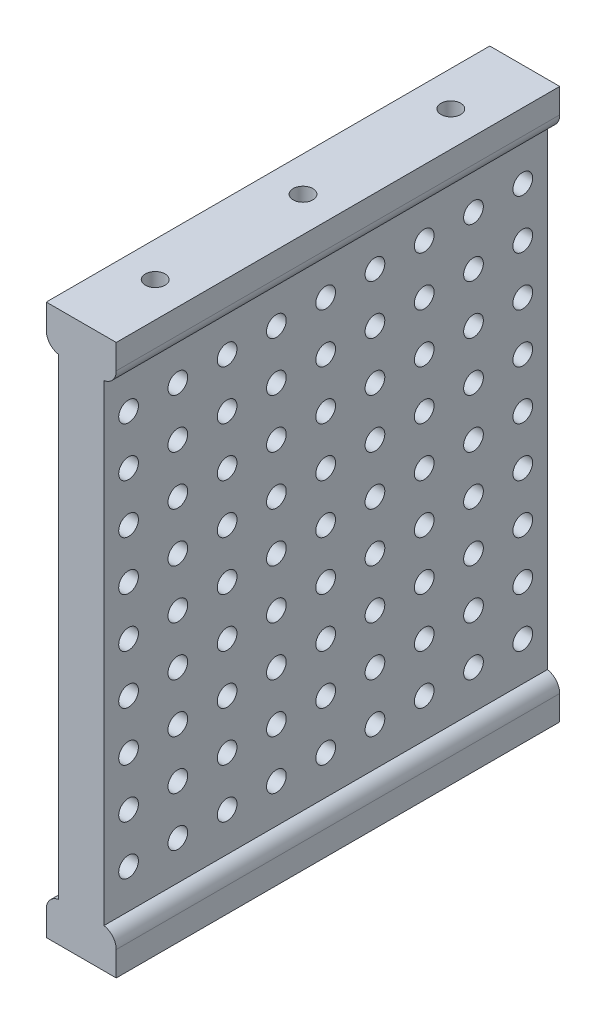
SolidWorks part; units mm, degrees
ref_plane "Plano frontal" through (0, 0, 0) normal (0, 0, 1) x (1, 0, 0)
ref_plane "Plano superior" through (0, 0, 0) normal (0, 1, 0) x (1, 0, 0)
ref_plane "Plano direito" through (0, 0, 0) normal (1, 0, 0) x (0, 0, -1)
sketch "Esboço1" plane through (0, 0, 0) normal (0, 0, 1) x (1, 0, 0)
  line L1 (10.95, -73.1295) -> (10.95, -73.1714)
  line L2 (1.75, -73.1295) -> (1.75, 22.6125)
  line L3 (1.75, 30.5705) -> (10.95, 30.5705)
  line L4 (10.95, -73.1295) -> (10.95, 22.6125)
  line L5 (-0.75, 30.5705) -> (13.45, 30.5705)
  line L6 (-0.75, 30.5705) -> (-0.75, 25.5705)
  line L7 (1.75, -73.1295) -> (1.75, -73.1714)
  line L8 (13.45, 30.5705) -> (13.45, 25.5705)
  line L9 (10.95, -73.1714) -> (10.95, -73.1295)
  line L10 (-0.75, -76.1295) -> (-0.75, -81.1295)
  line L11 (-0.75, -81.1295) -> (13.45, -81.1295)
  line L12 (13.45, -76.1295) -> (13.45, -81.1295)
  arc A0 (-0.75, -76.1295) -> (1.75, -73.1714) centre (2.25, -76.1295) cw
  arc A1 (13.45, -76.1295) -> (10.95, -73.1714) centre (10.45, -76.1295) ccw
  arc A2 (-0.75, 25.5705) -> (1.75, 22.6125) centre (2.25, 25.5705) ccw
  arc A3 (13.45, 25.5705) -> (10.95, 22.6125) centre (10.45, 25.5705) cw
  point P14 (-0.75, -73.1295)
  point P19 (-0.75, 22.5705)
  dimension "D9" = 3
  dimension "D10" = 3
  dimension "D11" = 3
  dimension "D12" = 3
  dimension "D1" = 103.7
  dimension "D2" = 9.2
  dimension "D3" = 14.2
  dimension "D4" = 2.5
  dimension "D5" = 14.2
  dimension "D6" = 2.5
  dimension "D7" = 8
  dimension "D8" = 8
extrude "Ressalto-extrusão2" add sketch "Esboço1" along normal blind 90 contours A3 L8 L5 L3 L6 A2 L2 L7 A0 L10 L11 L12 A1 L1 L4 region at (6.35, -25.2795, 0)
sketch "Esboço3" plane through (0, 0, 0) normal (0, 1, 0) x (1, 0, 0)
  line L0 (-0.75, 0) -> (13.45, -90) construction
  line L1 (13.45, -90) -> (-0.75, -90) construction
  line L2 (-0.75, -90) -> (13.45, 0) construction
  line L3 (13.45, 0) -> (6.35, 0) construction
  line L4 (-0.75, 0) -> (13.45, 0) construction
  line L5 (6.35, 0) -> (6.35, -90) construction
  line L6 (6.35, -45) -> (6.35, -15) construction
  line L7 (6.35, -45) -> (6.35, -75) construction
  circle A0 centre (6.35, -45) radius 2
  circle A1 centre (6.35, -15) radius 2
  circle A2 centre (6.35, -75) radius 2
  dimension "D1" = 4
  dimension "D2" = 2
  dimension "D3" = 30
  dimension "D5" = 30
  dimension "D4" = 2
extrude "Corte-extrusão1" cut sketch "Esboço3" against normal blind 90 and the other way blind 90
sketch "Esboço4" plane through (0, 0, 0) normal (1, 0, 0) x (0, 0, -1)
  line L5 (-45, -25.2795) -> (-35, -25.2795) construction
  line L6 (-45, -25.2795) -> (-55, -25.2795) construction
  line L7 (-45, -25.2795) -> (-45, -15.2795) construction
  line L8 (-45, -25.2795) -> (-45, -35.2795) construction
  circle A0 centre (-45, -25.2795) radius 2
  circle A1 centre (-35, -25.2795) radius 2
  circle A2 centre (-25, -25.2795) radius 2
  circle A3 centre (-15, -25.2795) radius 2
  circle A4 centre (-5, -25.2795) radius 2
  circle A5 centre (-35, -35.2795) radius 2
  circle A6 centre (-25, -35.2795) radius 2
  circle A7 centre (-15, -35.2795) radius 2
  circle A8 centre (-5, -35.2795) radius 2
  circle A9 centre (-35, -45.2795) radius 2
  circle A10 centre (-25, -45.2795) radius 2
  circle A11 centre (-15, -45.2795) radius 2
  circle A12 centre (-5, -45.2795) radius 2
  circle A13 centre (-35, -55.2795) radius 2
  circle A14 centre (-25, -55.2795) radius 2
  circle A15 centre (-15, -55.2795) radius 2
  circle A16 centre (-5, -55.2795) radius 2
  circle A17 centre (-35, -65.2795) radius 2
  circle A18 centre (-25, -65.2795) radius 2
  circle A19 centre (-15, -65.2795) radius 2
  circle A20 centre (-5, -65.2795) radius 2
  circle A21 centre (-45, -35.2795) radius 2
  circle A22 centre (-45, -45.2795) radius 2
  circle A23 centre (-45, -55.2795) radius 2
  circle A24 centre (-45, -65.2795) radius 2
  circle A25 centre (-55, -25.2795) radius 2
  circle A26 centre (-65, -25.2795) radius 2
  circle A27 centre (-75, -25.2795) radius 2
  circle A28 centre (-85, -25.2795) radius 2
  circle A29 centre (-55, -15.2795) radius 2
  circle A30 centre (-65, -15.2795) radius 2
  circle A31 centre (-75, -15.2795) radius 2
  circle A32 centre (-85, -15.2795) radius 2
  circle A33 centre (-55, -5.2795) radius 2
  circle A34 centre (-65, -5.2795) radius 2
  circle A35 centre (-75, -5.2795) radius 2
  circle A36 centre (-85, -5.2795) radius 2
  circle A37 centre (-55, 4.7205) radius 2
  circle A38 centre (-65, 4.7205) radius 2
  circle A39 centre (-75, 4.7205) radius 2
  circle A40 centre (-85, 4.7205) radius 2
  circle A41 centre (-55, 14.7205) radius 2
  circle A42 centre (-65, 14.7205) radius 2
  circle A43 centre (-75, 14.7205) radius 2
  circle A44 centre (-85, 14.7205) radius 2
  circle A45 centre (-45, -15.2795) radius 2
  circle A46 centre (-45, -5.2795) radius 2
  circle A47 centre (-45, 4.7205) radius 2
  circle A48 centre (-45, 14.7205) radius 2
  circle A49 centre (-45, -15.2795) radius 2
  circle A50 centre (-45, -5.2795) radius 2
  circle A51 centre (-45, 4.7205) radius 2
  circle A52 centre (-45, 14.7205) radius 2
  circle A53 centre (-35, -15.2795) radius 2
  circle A54 centre (-35, -5.2795) radius 2
  circle A55 centre (-35, 4.7205) radius 2
  circle A56 centre (-35, 14.7205) radius 2
  circle A57 centre (-25, -15.2795) radius 2
  circle A58 centre (-25, -5.2795) radius 2
  circle A59 centre (-25, 4.7205) radius 2
  circle A60 centre (-25, 14.7205) radius 2
  circle A61 centre (-15, -15.2795) radius 2
  circle A62 centre (-15, -5.2795) radius 2
  circle A63 centre (-15, 4.7205) radius 2
  circle A64 centre (-15, 14.7205) radius 2
  circle A65 centre (-5, -15.2795) radius 2
  circle A66 centre (-5, -5.2795) radius 2
  circle A67 centre (-5, 4.7205) radius 2
  circle A68 centre (-5, 14.7205) radius 2
  circle A69 centre (-35, -25.2795) radius 2
  circle A70 centre (-25, -25.2795) radius 2
  circle A71 centre (-15, -25.2795) radius 2
  circle A72 centre (-5, -25.2795) radius 2
  circle A73 centre (-45, -35.2795) radius 2
  circle A74 centre (-45, -45.2795) radius 2
  circle A75 centre (-45, -55.2795) radius 2
  circle A76 centre (-45, -65.2795) radius 2
  circle A77 centre (-55, -35.2795) radius 2
  circle A78 centre (-55, -45.2795) radius 2
  circle A79 centre (-55, -55.2795) radius 2
  circle A80 centre (-55, -65.2795) radius 2
  circle A81 centre (-65, -35.2795) radius 2
  circle A82 centre (-65, -45.2795) radius 2
  circle A83 centre (-65, -55.2795) radius 2
  circle A84 centre (-65, -65.2795) radius 2
  circle A85 centre (-75, -35.2795) radius 2
  circle A86 centre (-75, -45.2795) radius 2
  circle A87 centre (-75, -55.2795) radius 2
  circle A88 centre (-75, -65.2795) radius 2
  circle A89 centre (-85, -35.2795) radius 2
  circle A90 centre (-85, -45.2795) radius 2
  circle A91 centre (-85, -55.2795) radius 2
  circle A92 centre (-85, -65.2795) radius 2
  circle A93 centre (-55, -25.2795) radius 2
  circle A94 centre (-65, -25.2795) radius 2
  circle A95 centre (-75, -25.2795) radius 2
  circle A96 centre (-85, -25.2795) radius 2
  dimension "D1" = 4
  dimension "D4" = 10
  dimension "D7" = 10
  dimension "D10" = 10
  dimension "D13" = 10
  dimension "D2" = 5
  dimension "D3" = 5
  dimension "D5" = 5
  dimension "D6" = 5
  dimension "D8" = 5
  dimension "D9" = 5
  dimension "D11" = 5
  dimension "D12" = 5
extrude "Corte-extrusão2" cut sketch "Esboço4" along direction (1, 0, 0) on the side against the normal blind 90 and the other way blind 90 contours A44 | A43 | A42 | A41 | A48 | A56 | A60 | A64 | A68 | A67 | A63 | A59 | A55 | A47 | A37 | A38 | A39 | A40 | A36 | A35 | A34 | A33 | A46 | A54 | A58 | A62 | A66 | A65 | A61 | A57 | A53 | A45 | A29 | A30 | A31 | A32 | A28 | A27 | A26 | A25 | A2 | A3 | A4 | A8 | A7 | A6 | A5 | A21 | A77 | A81 | A85 | A89 | A90 | A86 | A82 | A78 | A22 | A9 | A10 | A11 | A12 | A14 | A13 | A23 | A83 | A87 | A91 | A92 | A88 | A84 | A80 | A24 | A17 | A18 | A19 | A20
sketch "Esboço5" plane through (0, 0, 0) normal (1, 0, 0) x (0, 0, -1)
  line L0 (-45, -25.2795) -> (-35, -25.2795) construction
  line L1 (-15, -55.2795) -> (-5, -55.2795) construction
  circle A0 centre (-45, -25.2795) radius 2
  circle A1 centre (-55, -25.2795) radius 2 construction
  arc A2 (-47, -15.2795) -> (-43, -15.2795) centre (-45, -15.2795) ccw construction
  circle A3 centre (-35, -25.2795) radius 2
  circle A4 centre (-15, -55.2795) radius 2
  circle A5 centre (-25, -55.2795) radius 2 construction
  circle A6 centre (-15, -45.2795) radius 2 construction
  circle A7 centre (-5, -55.2795) radius 2
  circle A8 centre (-55, -55.2795) radius 2
  circle A9 centre (-65, -55.2795) radius 2 construction
  point P4 (-45, -17.2795)
  dimension "D1" = 4
  dimension "D6" = 4
  dimension "D7" = 10
  dimension "D8" = 10
  dimension "D11" = 4
  dimension "D12" = 10
  dimension "D2" = 10
  dimension "D3" = 8
  dimension "D5" = 10
  dimension "D10" = 10
  dimension "D4" = 2
  dimension "D9" = 2
extrude "Corte-extrusão3" cut sketch "Esboço5" along direction (1, 0, 0) on the side of the normal blind 53 and the other way blind 22
